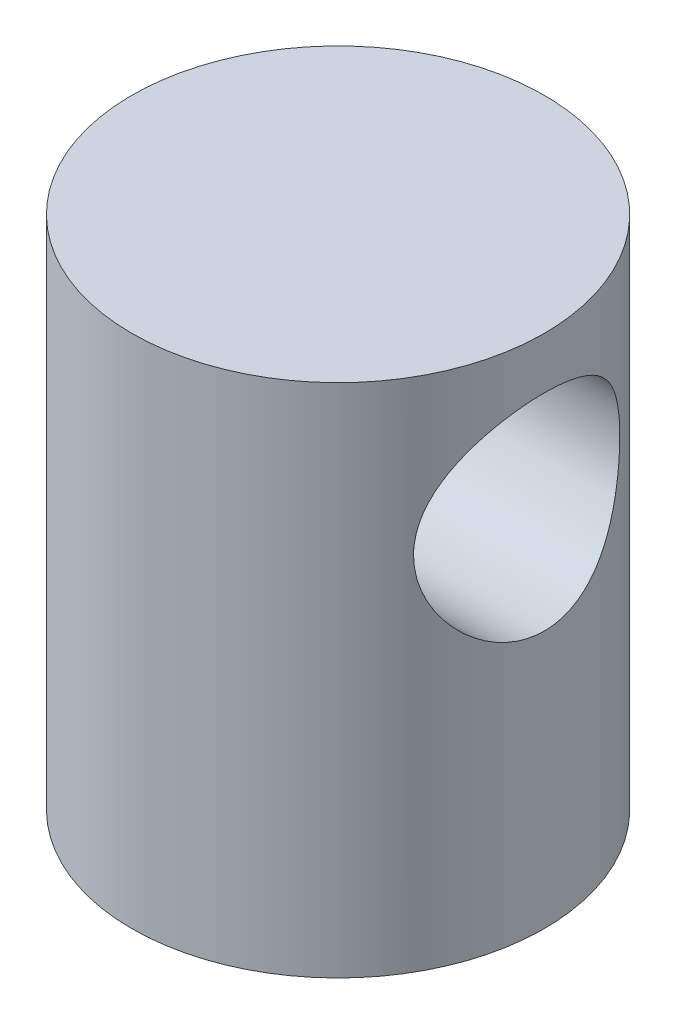
SolidWorks part; units mm, degrees
ref_plane "Front Plane" through (0, 0, 0) normal (0, 0, 1) x (1, 0, 0)
ref_plane "Top Plane" through (0, 0, 0) normal (0, 1, 0) x (1, 0, 0)
ref_plane "Right Plane" through (0, 0, 0) normal (1, 0, 0) x (0, 0, -1)
sketch "Sketch1" plane through (0, 0, 0) normal (0, 1, 0) x (1, 0, 0)
  circle A0 centre (0, 0) radius 20
  dimension "D1" = 40
extrude "Boss-Extrude1" add sketch "Sketch1" along normal blind 50
sketch "Sketch2" plane through (0, 0, 0) normal (1, 0, 0) x (0, 0, -1)
  line L0 (0, 50) -> (0, 35) construction
  line L1 (20, 50) -> (-20, 50) construction
  circle A0 centre (0, 35) radius 10
  dimension "D2" = 20
  dimension "D1" = 15
extrude "Cut-Extrude1" cut sketch "Sketch2" against normal blind 50 and the other way blind 50
ref_axis "Axis1" through (0, -2.5, 0) along (0, 1, 0)
ref_axis "Axis2" through (20, 35, 0) along (-1, 0, 0)
